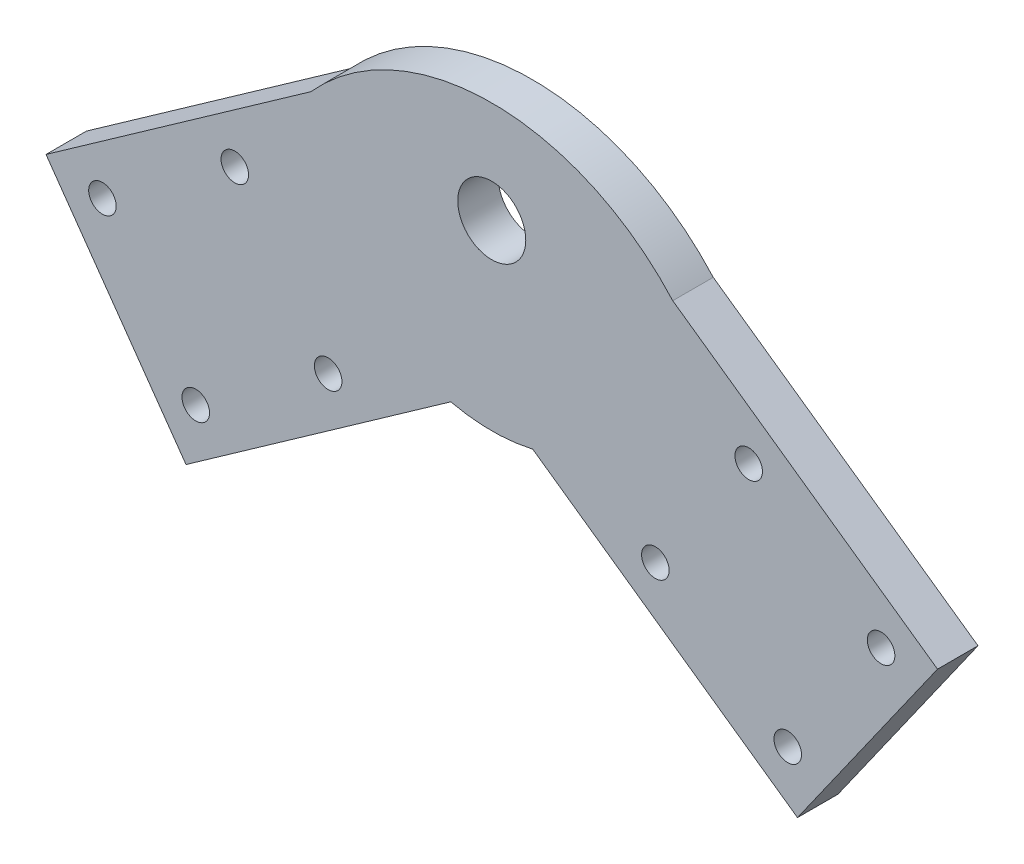
SolidWorks part; units mm, degrees
material "PLA 15%"
ref_plane "Front Plane" through (0, 0, 0) normal (0, 0, 1) x (1, 0, 0)
ref_plane "Top Plane" through (0, 0, 0) normal (0, 1, 0) x (1, 0, 0)
ref_plane "Right Plane" through (0, 0, 0) normal (1, 0, 0) x (0, 0, -1)
sketch "Sketch2" plane through (0, 0, 0) normal (0, 0, 1) x (1, 0, 0)
  line L8 (0, 0) -> (0, -22.5) construction
  line L9 (0, 0) -> (5.0614, -21.9233) construction
  line L10 (0, 0) -> (-5.0614, -21.9233) construction
  line L11 (5.0614, -21.9233) -> (22.35, 2.5941) construction
  line L12 (5.0614, -21.9233) -> (37.7513, -44.9747)
  line L13 (22.35, 2.5941) -> (55.0399, -20.4573)
  line L14 (37.7513, -44.9747) -> (55.0399, -20.4573)
  line L15 (-5.0614, -21.9233) -> (-22.35, 2.5941) construction
  line L16 (-5.0614, -21.9233) -> (-37.7513, -44.9747)
  line L17 (-22.35, 2.5941) -> (-55.0399, -20.4573)
  line L18 (-37.7513, -44.9747) -> (-55.0399, -20.4573)
  line L28 (-36.5465, -38.0071) -> (-20.2016, -26.4814) construction
  line L29 (-12.0291, -20.7185) -> (-23.5548, -4.3735) construction
  line L30 (20.2016, -26.4814) -> (31.7273, -10.1364) construction
  line L32 (31.7273, -10.1364) -> (48.0722, -21.6621) construction
  line L37 (20.2016, -26.4814) -> (36.5465, -38.0071) construction
  line L38 (36.5465, -38.0071) -> (48.0722, -21.6621) construction
  line L39 (-23.5548, -4.3735) -> (-48.0722, -21.6621) construction
  line L40 (-31.7273, -10.1364) -> (-48.0722, -21.6621) construction
  line L42 (-12.0291, -20.7185) -> (-36.5465, -38.0071) construction
  line L43 (-36.5465, -38.0071) -> (-48.0722, -21.6621) construction
  line L45 (-48.0722, -21.6621) -> (-36.5465, -38.0071) construction
  line L46 (-36.5465, -38.0071) -> (-20.2016, -26.4814) construction
  line L47 (-20.2016, -26.4814) -> (-31.7273, -10.1364) construction
  line L48 (-31.7273, -10.1364) -> (-48.0722, -21.6621) construction
  arc A0 (-5.0614, -21.9233) -> (5.0614, -21.9233) centre (0, 0) ccw
  arc A3 (-22.35, 2.5941) -> (-21.0669, -7.9017) centre (0, 0) ccw construction
  arc A4 (-21.0669, -7.9017) -> (-14.517, -17.1903) centre (0, 0) ccw construction
  arc A5 (-14.517, -17.1903) -> (-5.0614, -21.9233) centre (0, 0) ccw construction
  arc A6 (5.0614, -21.9233) -> (14.517, -17.1903) centre (0, 0) ccw construction
  arc A8 (14.517, -17.1903) -> (21.0669, -7.9017) centre (0, 0) ccw construction
  arc A9 (21.0669, -7.9017) -> (22.35, 2.5941) centre (0, 0) ccw construction
  circle A12 centre (0, 0) radius 4.2
  arc A15 (-22.35, 2.5941) -> (22.35, 2.5941) centre (0, -17.4179) cw
  dimension "D5" = 45
  dimension "D8" = 8.4
  dimension "D10" = 30
  dimension "D1" = 13
  dimension "D2" = 13
  dimension "D3" = 30
  dimension "D4" = 30
  dimension "D6" = 40
  dimension "D7" = 40
  dimension "D11" = 20
  dimension "D12" = 20
  dimension "D13" = 5
  dimension "D14" = 5
  dimension "D15" = 5
  dimension "D16" = 20
  dimension "D9" = 5
extrude "Boss-Extrude1" add sketch "Sketch2" along normal blind 5
hole_wizard "M3 Clearance Hole1" positions "Sketch8" profile "Sketch9" hole size "M3" standard "ANSI Metric" end condition through all
sketch "Sketch8" plane through (0, 0, 5) normal (0, 0, 1) x (1, 0, 0)
  point P24 (-31.7273, -10.1364)
  point P27 (-20.2016, -26.4814)
  point P30 (-36.5465, -38.0071)
  point P33 (-48.0722, -21.6621)
  point P36 (31.7273, -10.1364)
  point P39 (48.0722, -21.6621)
  point P42 (20.2016, -26.4814)
  point P45 (36.5465, -38.0071)
sketch "Sketch9" plane through (-31.7273, -10.1364, 5) normal (1, 0, 0) x (0, -1, 0)
  line L0 (0, 0) -> (0, 5)
  line L1 (0, 5) -> (1.7, 5)
  line L2 (1.7, 5) -> (1.7, 0)
  line L5 (1.7, 0) -> (0, 0)
  line L11 (0, -6.35) -> (0, 107.95) construction
  dimension "Thru Hole Dia." = 3.4
  dimension "Thru Hole Depth" = 5
